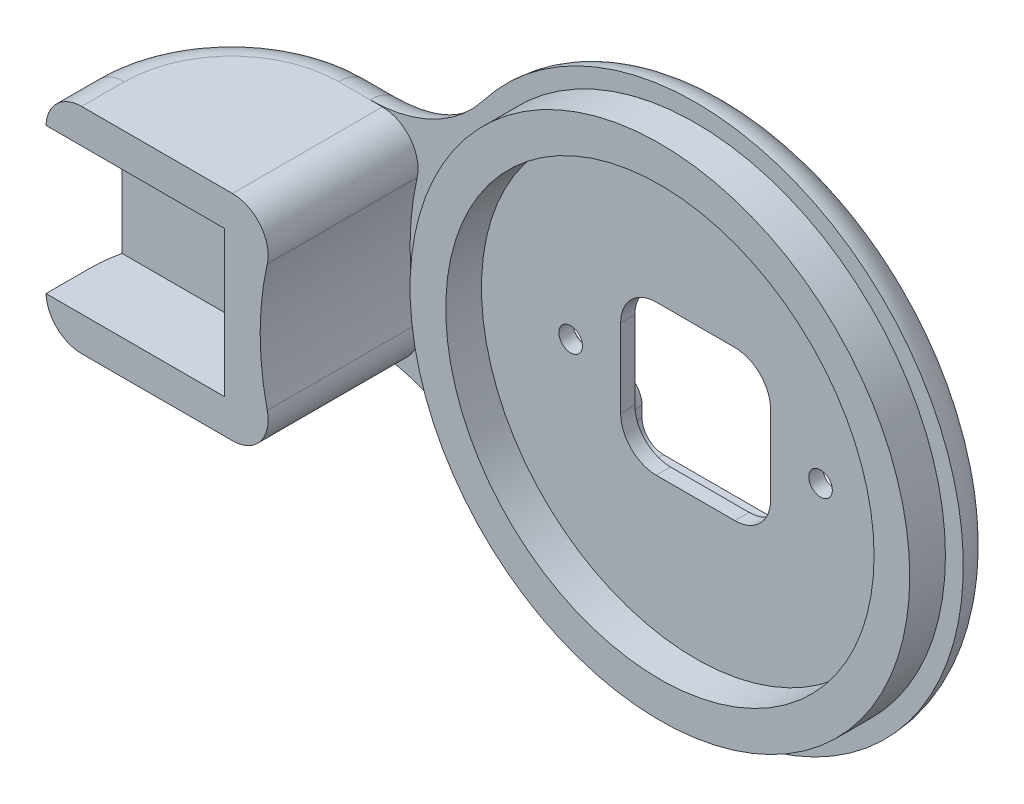
SolidWorks part; units mm, degrees
ref_plane "Plan de face" through (0, 0, 0) normal (0, 0, 1) x (1, 0, 0)
ref_plane "Plan de dessus" through (0, 0, 0) normal (0, 1, 0) x (1, 0, 0)
ref_plane "Plan de droite" through (0, 0, 0) normal (1, 0, 0) x (0, 0, -1)
sketch "Esquisse1" plane through (0, 0, 0) normal (0, 0, 1) x (1, 0, 0)
  line L0 (-1000, 0) -> (49000, 0) construction
  line L1 (-45.6207, 15) -> (-70, 15)
  line L4 (-70, -15) -> (-70, 15)
  line L5 (-45.6207, -15) -> (-70, -15)
  arc A0 (-29.7526, -22.8261) -> (-29.7526, 22.8261) centre (0, 0) ccw
  arc A2 (-45.6207, 15) -> (-29.7526, 22.8261) centre (-45.6207, 35) ccw
  arc A3 (-45.6207, -15) -> (-29.7526, -22.8261) centre (-45.6207, -35) cw
  point P8 (-34.3693, -15)
  point P9 (-70, 0)
  point P13 (-70, 0)
  point P20 (-34.3693, 15)
  dimension "D1" = 75
  dimension "D5" = 20
  dimension "D2" = 15
  dimension "D3" = 70
extrude "Boss.-Extru.1" add sketch "Esquisse1" along normal blind 5
sketch "Esquisse6" plane through (0, 0, 5) normal (0, 0, 1) x (1, 0, 0)
  circle A0 centre (0, 0) radius 35
  circle A1 centre (0, 0) radius 30
  dimension "D1" = 70
  dimension "D2" = 60
extrude "Boss.-Extru.6" add sketch "Esquisse6" along normal blind 5
sketch "Esquisse8" plane through (0, 0, 5) normal (0, 0, 1) x (1, 0, 0)
  line L1 (-1000, 0) -> (49000, 0) construction
  line L3 (-70, -15) -> (-70, 15)
  line L9 (-70, -15) -> (-43.8748, -15)
  line L10 (-70, 15) -> (-43.8748, 15)
  line L20 (-70, 15) -> (-70, -15) construction
  arc A2 (-38.9998, 8.8889) -> (-38.9998, -8.8889) centre (0, 0) ccw
  arc A3 (-43.8748, 15) -> (-38.9998, 8.8889) centre (-43.8748, 10) cw
  arc A4 (-43.8748, -15) -> (-38.9998, -8.8889) centre (-43.8748, -10) ccw
  point P5 (-70, 0)
  point P15 (-70, 0)
  dimension "D1" = 80
  dimension "D2" = 5
extrude "Boss.-Extru.9" add sketch "Esquisse8" along normal blind 21
fillet "Congé1" radius 20 1 edges at (-70, 0, 0)
fillet "Congé2" radius 5 9 edges at (-47.8104, -15, 0) (-36.7742, -17.0629, 0) (37.5, 0, 0) (-36.7742, 17.0629, 0) (-47.8104, 15, 0) (-64.1421, 15, 5.8579) (-64.1421, -15, 5.8579) (-70, -15, 23) (-70, 15, 23)
sketch "Esquisse11" plane through (-70, 0, 0) normal (-1, 0, 0) x (0, 0, 1)
  line L0 (26, 10) -> (20, 10) construction
  line L1 (16, 10) -> (36, 10) construction
  line L2 (16, 10) -> (16, -10) construction
  line L3 (16, -10) -> (36, -10) construction
  line L4 (36, 10) -> (36, -10) construction
  line L5 (20, -10) -> (26, -10) construction
  line L6 (0, -10) -> (0, 10) construction
  line L7 (15.8, 10.2) -> (36.2, 10.2)
  line L8 (36.2, 10.2) -> (36.2, -10.2)
  line L9 (15.8, -10.2) -> (36.2, -10.2)
  line L10 (15.8, 10.2) -> (15.8, -10.2)
  dimension "D1" = 16
  dimension "D2" = 20
  dimension "D3" = 0.2
extrude "Enlèv. mat.-Extru.2" cut sketch "Esquisse11" against normal blind 25
sketch "Esquisse12" plane through (0, 0, 15.8) normal (0, 0, 1) x (1, 0, 0)
  line L0 (-69.554, 10) -> (-69.554, -10) construction
  circle A0 centre (-49.554, 0) radius 2.6
  dimension "D1" = 5.2
  dimension "D2" = 20
extrude "Enlèv. mat.-Extru.3" cut sketch "Esquisse12" against normal through all
sketch "Esquisse13" plane through (0, 0, 15.8) normal (0, 0, 1) x (1, 0, 0)
  circle A0 centre (-49.554, 0) radius 4.5
  dimension "D1" = 9
extrude "Enlèv. mat.-Extru.4" cut sketch "Esquisse13" against normal through all from offset 5 offset against normal yes
sketch "Esquisse14" plane through (0, 0, 5) normal (0, 0, 1) x (1, 0, 0)
  line L6 (-5.5, 10.5) -> (5.5, 10.5)
  line L11 (-1000, 0) -> (49000, 0) construction
  line L16 (-10.5, 5.5) -> (-10.5, -5.5)
  line L17 (-5.5, -10.5) -> (5.5, -10.5)
  line L18 (10.5, 5.5) -> (10.5, -5.5)
  line L19 (-10.5, 10.5) -> (10.5, -10.5) construction
  line L20 (-10.5, -10.5) -> (10.5, 10.5) construction
  arc A8 (-10.5, -5.5) -> (-5.5, -10.5) centre (-5.5, -5.5) ccw
  arc A9 (5.5, -10.5) -> (10.5, -5.5) centre (5.5, -5.5) ccw
  arc A10 (5.5, 10.5) -> (10.5, 5.5) centre (5.5, 5.5) cw
  arc A11 (-5.5, 10.5) -> (-10.5, 5.5) centre (-5.5, 5.5) ccw
  point P0 (0, 0)
  dimension "D2" = 5
  dimension "D1" = 21
extrude "Enlèv. mat.-Extru.5" cut sketch "Esquisse14" against normal blind 2
sketch "Esquisse17" plane through (0, 0, 0) normal (0, 0, -1) x (-1, 0, 0)
  line L0 (15.5, 5) -> (19.5, 5)
  line L1 (-9.5, 12.5) -> (9.5, 12.5)
  line L3 (-9.5, -12.5) -> (9.5, -12.5)
  line L4 (12.5, 9.5) -> (12.5, 8)
  line L5 (12.5, -8) -> (12.5, -9.5)
  line L6 (0, -1000) -> (0, 49000) construction
  line L10 (22.5, -2) -> (22.5, 2)
  line L11 (-12.5, -8) -> (-12.5, -9.5)
  line L12 (-15.5, -5) -> (-19.5, -5)
  line L13 (-22.5, -2) -> (-22.5, 2)
  line L14 (-15.5, 5) -> (-19.5, 5)
  line L15 (15.5, -5) -> (19.5, -5)
  line L16 (-12.5, 9.5) -> (-12.5, 8)
  arc A0 (19.5, -5) -> (22.5, -2) centre (19.5, -2) ccw
  arc A1 (19.5, 5) -> (22.5, 2) centre (19.5, 2) cw
  arc A2 (15.5, 5) -> (12.5, 8) centre (15.5, 8) cw
  arc A3 (15.5, -5) -> (12.5, -8) centre (15.5, -8) ccw
  arc A4 (9.5, -12.5) -> (12.5, -9.5) centre (9.5, -9.5) ccw
  arc A5 (-12.5, -9.5) -> (-9.5, -12.5) centre (-9.5, -9.5) ccw
  arc A6 (9.5, 12.5) -> (12.5, 9.5) centre (9.5, 9.5) cw
  arc A7 (-9.5, 12.5) -> (-12.5, 9.5) centre (-9.5, 9.5) ccw
  arc A8 (-15.5, -5) -> (-12.5, -8) centre (-15.5, -8) cw
  arc A9 (-19.5, -5) -> (-22.5, -2) centre (-19.5, -2) cw
  arc A10 (-19.5, 5) -> (-22.5, 2) centre (-19.5, 2) ccw
  arc A11 (-15.5, 5) -> (-12.5, 8) centre (-15.5, 8) ccw
  point P0 (0, 0)
  point P6 (12.5, 0)
  point P13 (22.5, -5)
  point P16 (22.5, 5)
  point P21 (12.5, -5)
  point P28 (12.5, 12.5)
  point P31 (-12.5, 12.5)
  dimension "D4" = 3
  dimension "D1" = 25
  dimension "D2" = 10
  dimension "D3" = 10
extrude "Enlèv. mat.-Extru.7" cut sketch "Esquisse17" against normal blind 3
sketch "Esquisse19" plane through (0, 0, 3) normal (0, 0, -1) x (-1, 0, 0)
  line L0 (0, -1000) -> (0, 49000) construction
  line L1 (22.5, -2) -> (22.5, 2) construction
  circle A0 centre (17.5, 0) radius 1.65
  circle A1 centre (-17.5, 0) radius 1.65
  dimension "D2" = 3.3
  dimension "D1" = 5
extrude "Enlèv. mat.-Extru.8" cut sketch "Esquisse19" against normal through all
